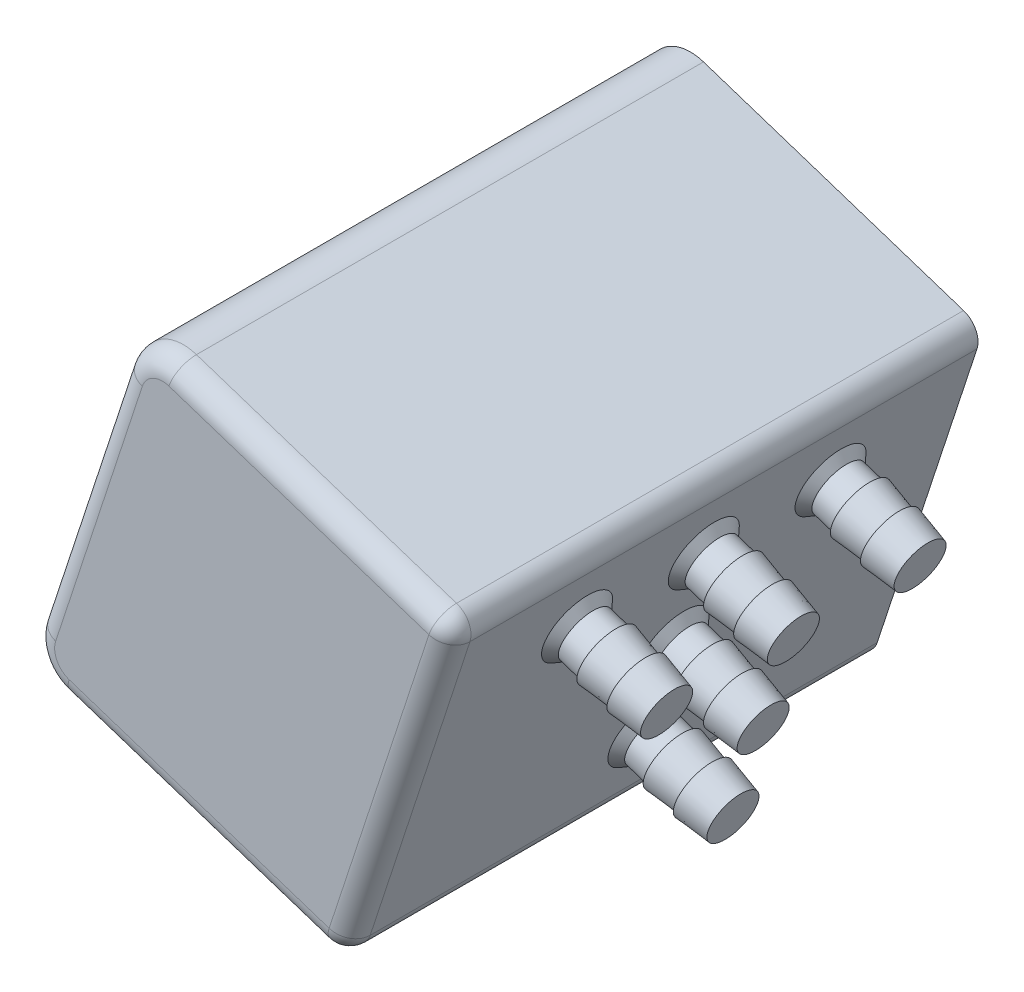
SolidWorks part; units mm, degrees
material "PET"
ref_plane "Front Plane" through (0, 0, 0) normal (0, 0, 1) x (1, 0, 0)
ref_plane "Top Plane" through (0, 0, 0) normal (0, 1, 0) x (1, 0, 0)
ref_plane "Right Plane" through (0, 0, 0) normal (1, 0, 0) x (0, 0, -1)
sketch "Sketch1" plane through (0, 0, 0) normal (0, 0, 1) x (1, 0, 0)
  line L0 (290.2809, 502.98) -> (307.3073, 554.8844) construction
  line L1 (290.2809, 502.98) -> (307.3073, 554.8844)
  line L2 (307.3073, 554.8844) -> (417.2514, 518.8189) construction
  line L4 (307.3073, 554.8844) -> (355.5766, 539.0504)
  line L5 (338.5502, 487.146) -> (290.2809, 502.98)
  line L6 (355.5766, 539.0504) -> (338.5502, 487.146)
  line L7 (247.2747, 82.1423) -> (332.9427, 343.2977) construction
  line L10 (316.9169, 494.2424) -> (290.2809, 502.98) construction
  dimension "D1" = 50.8
extrude "Boss-Extrude1" add sketch "Sketch1" along normal offset from surface (79.6427 mm away) 3.175
fillet "Fillet1" radius 6.35 2 edges at (307.3073, 554.8844, 39.8213) (290.2809, 502.98, 39.8213)
fillet "Fillet2" radius 3.175 8 edges at (347.0634, 513.0982, 79.6427) (317.4323, 494.0734, 79.6427) (292.6278, 504.1675, 79.6427) (298.7941, 528.9322, 79.6427) (308.4948, 552.5375, 79.6427) (334.4588, 545.9778, 79.6427) (355.5766, 539.0504, 39.8213) (338.5502, 487.146, 39.8213)
sketch "Sketch5" plane through (161.3834, -52.9394, 0) normal (0.9502, -0.3117, 0) x (0, 0, -1)
  line L0 (-38.2338, 571.5765) -> (-38.2338, 619.8522) construction
  line L3 (-76.4677, 610.3272) -> (-38.2338, 610.3272) construction
  line L5 (0, 571.5765) -> (0, 619.8522) construction
  line L6 (-38.2338, 610.3272) -> (0, 610.3272) construction
  line L8 (-76.4677, 619.8522) -> (-76.4677, 571.5765) construction
  line L9 (0, 619.8522) -> (-76.4677, 619.8522) construction
  line L10 (-76.4677, 571.5765) -> (0, 571.5765) construction
  point P7 (-38.2338, 610.3272)
  point P9 (-38.2338, 595.7143)
  point P11 (-38.2338, 581.1015)
  point P15 (-57.3508, 610.3272)
  point P17 (-19.1169, 610.3272)
  point P33 (-19.1169, 610.3272)
  dimension "D1" = 9.525
  dimension "D2" = 9.525
ref_plane "Plane1" through (0, 0, 38.2338) normal (0, 0, 1) x (1, 0, 0)
sketch "Sketch6" plane through (0, 0, 38.2338) normal (0, 0, 1) x (1, 0, 0)
  line L0 (342.5087, 499.2133) -> (365.0021, 491.8347)
  line L1 (339.5398, 490.1628) -> (354.587, 536.0336) construction
  line L3 (365.0021, 491.8347) -> (366.1422, 495.31)
  line L13 (348.2368, 501.3861) -> (343.7087, 502.8715)
  line L14 (348.3952, 501.8688) -> (348.2368, 501.3861)
  line L15 (352.7132, 499.8671) -> (348.3952, 501.8688)
  line L16 (352.8715, 500.3498) -> (352.7132, 499.8671)
  line L17 (357.1895, 498.3481) -> (352.8715, 500.3498)
  line L18 (357.3479, 498.8308) -> (357.1895, 498.3481)
  line L19 (361.6659, 496.8291) -> (357.3479, 498.8308)
  line L20 (361.8242, 497.3118) -> (361.6659, 496.8291)
  line L21 (366.1422, 495.31) -> (361.8242, 497.3118)
  line L22 (343.7087, 502.8715) -> (342.5087, 499.2133)
  dimension "D1" = 23.6728
  dimension "D2" = 3.6576
  dimension "D3" = 6.71
  dimension "D4" = 4.318
  dimension "D5" = 0.508
revolve "Revolve1" add sketch "Sketch6" angle 360 about L0
sketch "Sketch7" plane through (183.8769, -60.318, 0) normal (0.9502, -0.3117, 0) x (0, 0, -1)
  circle A0 centre (-38.2338, 581.1015) radius 4.2618 construction
  circle A1 centre (-38.2338, 581.1015) radius 4.2618
extrude "Cut-Extrude1" cut sketch "Sketch7" against normal up to surface (9.4536 mm away) up to face at (354.8495, 491.2145, 38.2338)
chamfer "Chamfer1" distance 1.27 angle 45 1 edges at (341.3086, 495.5551, 38.2338)
pattern_sketch "Sketch-Pattern2" of "Chamfer1", "Revolve1", "Cut-Extrude1" driven by "Sketch5"
hole_wizard "Hole1" positions "Sketch8" profile "Sketch9" legacy
sketch "Sketch8" plane through (0, 0, 0) normal (0, 0, -1) x (-1, 0, 0)
  line L2 (-347.0634, 513.0982) -> (-324.4371, 520.5204) construction
  line L3 (-339.5398, 490.1628) -> (-354.587, 536.0336) construction
  line L4 (-324.4371, 520.5204) -> (-332.9504, 546.4726) construction
  line L5 (-352.5598, 540.04) -> (-313.341, 552.9051) construction
  line L7 (-296.3145, 501.0007) -> (-335.5333, 488.1356) construction
  point P9 (-332.4685, 499.1653)
  point P24 (-343.5572, 532.9688)
  point P26 (-305.3171, 508.072)
  point P27 (-316.4058, 541.8754)
  dimension "D1" = 9.525
  dimension "D2" = 9.525
sketch "Sketch9" plane through (332.4685, 499.1653, 0) normal (1, 0, 0) x (0, 1, 0)
  line L0 (0, 0) -> (0, 4.699)
  line L1 (0, 4.699) -> (2.8702, 4.699)
  line L2 (2.8702, 4.699) -> (2.9972, 0)
  line L3 (2.9972, 0) -> (0, 0)
  line L4 (0, 110) -> (0, -10) construction
  dimension "Minor Diameter" = 5.7404
  dimension "Depth" = 4.699
  dimension "Major Diameter" = 5.9944
hole_wizard "#8 Clearance Hole1" positions "Sketch10" profile "Sketch11" hole size "#8" standard "ANSI Inch"
sketch "Sketch10" plane through (0, 0, 0) normal (0, 0, -1) x (-1, 0, 0)
  point P0 (-332.4685, 499.1653)
  point P3 (-343.5572, 532.9688)
  point P6 (-316.4058, 541.8754)
  point P9 (-305.3171, 508.072)
sketch "Sketch11" plane through (332.4685, 499.1653, 0) normal (1, 0, 0) x (0, 1, 0)
  line L0 (0, 0) -> (0, 14.1766)
  line L1 (0, 14.1766) -> (2.4574, 12.7)
  line L2 (2.4574, 12.7) -> (2.4574, 0)
  line L5 (2.4574, 0) -> (0, 0)
  line L10 (0, 14.1766) -> (-2.4575, 12.7) construction
  line L11 (0, -6.35) -> (0, 107.95) construction
  dimension "Hole Dia." = 4.9149
  dimension "Hole Depth" = 12.7
  dimension "Drill Angle" = 118
